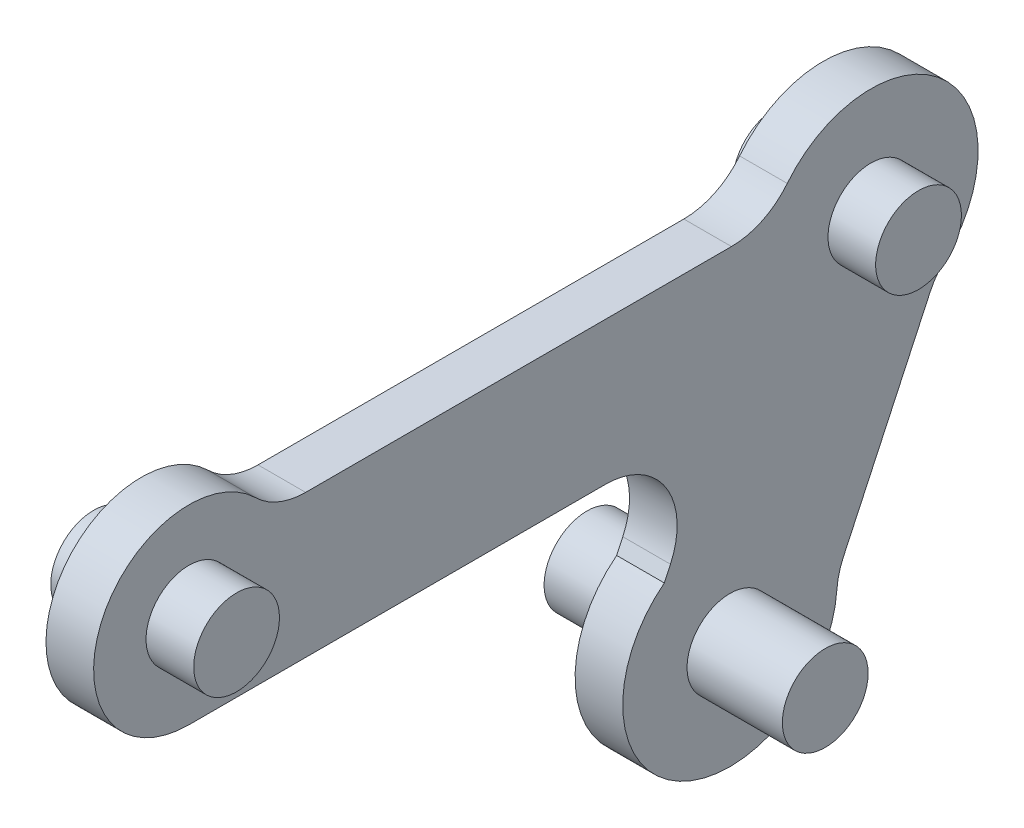
SolidWorks part; units mm, degrees
ref_plane "前视基准面" through (0, 0, 0) normal (0, 0, 1) x (1, 0, 0)
ref_plane "上视基准面" through (0, 0, 0) normal (0, 1, 0) x (1, 0, 0)
ref_plane "右视基准面" through (0, 0, 0) normal (1, 0, 0) x (0, 0, -1)
other "Configuration Table"
sketch "草图1" plane through (0, 0, 0) normal (1, 0, 0) x (0, 0, -1)
  line L1 (-25, 0) -> (0, 0)
  line L2 (-25, 0) -> (-25, -6)
  line L3 (-25, -6) -> (0, -6)
  line L4 (0, 0) -> (0, -6)
  line L5 (0, 0) -> (7.2505, -3.3809)
  line L6 (0, 0) -> (-5.9167, -12.6883)
  line L7 (-5.9167, -12.6883) -> (1.3338, -16.0693)
  line L8 (7.2505, -3.3809) -> (1.3338, -16.0693)
  circle A0 centre (-25, -2) radius 4
  circle A1 centre (3.6252, -1.6905) radius 4.5
  circle A2 centre (-2.2914, -14.3788) radius 4.5
  circle A3 centre (-25, -2) radius 2
  circle A4 centre (3.6252, -1.6905) radius 2
  circle A5 centre (-2.2914, -14.3788) radius 2
  dimension "D5" = 8
  dimension "D6" = 9
  dimension "D7" = 9
  dimension "D9" = 4
  dimension "D1" = 6
  dimension "D2" = 8
  dimension "D3" = 65
  dimension "D4" = 25
  dimension "D8" = 14
extrude "凸台-拉伸1" add sketch "草图1" along normal blind 2 contours A0 | L1 L4 L3 L2 | A1 | L5 L8 L7 L6 | A2
extrude "切除-拉伸1" cut sketch "草图1<3>" along normal through all contours A3 | A4 | A5
sketch "草图1<3>" plane through (0, 0, 0) normal (1, 0, 0) x (0, 0, -1) same geometry as "草图1"
fillet "圆角1" radius 3 5 edges at (1, -14.2009, -2.2051) (1, -5.2493, -6.3792) (1, 0, 0.5452) (1, 0, 21.5359) (1, -6, 2.7978)
sketch "草图2" plane through (2, 0, 0) normal (1, 0, 0) x (0, 0, -1)
  circle A0 centre (3.6252, -1.6905) radius 2
  circle A1 centre (-2.2914, -14.3788) radius 2
  circle A2 centre (-25, -2) radius 2
  circle A3 centre (3.6252, -1.6905) radius 1.8
  circle A4 centre (-2.2914, -14.3788) radius 1.8
  circle A5 centre (-25, -2) radius 1.8
  point P12 (0, 0)
  dimension "D1" = 4
  dimension "D2" = 3.6
extrude "凸台-拉伸2" add sketch "草图2" against normal up to surface (2 mm away) contours A2 | A0 | A1 up to face at (0, -2, 23)
extrude "凸台-拉伸5" add sketch "草图2<5>" along normal blind 2 contours A5 | A3 region at (2, -1.6905, -3.6252) region at (2, -2, 25)
sketch "草图2<5>" plane through (2, 0, 0) normal (1, 0, 0) x (0, 0, -1) same geometry as "草图2"
extrude "凸台-拉伸6" add sketch "草图2<6>" against normal blind 2 from surface contours A5 | A3 region at (2, -1.6905, -3.6252) region at (2, -2, 25) starting at face at (0, -5.8195, 6.0803)
sketch "草图2<6>" plane through (2, 0, 0) normal (1, 0, 0) x (0, 0, -1) same geometry as "草图2"
extrude "凸台-拉伸7" add sketch "草图2<7>" along normal blind 4 contours A4 region at (2, -14.3788, 2.2914)
sketch "草图2<7>" plane through (2, 0, 0) normal (1, 0, 0) x (0, 0, -1) same geometry as "草图2"
extrude "凸台-拉伸8" add sketch "草图2<8>" against normal blind 4 from surface contours A4 region at (2, -14.3788, 2.2914) starting at face at (0, -1.6905, -5.4252)
sketch "草图2<8>" plane through (2, 0, 0) normal (1, 0, 0) x (0, 0, -1) same geometry as "草图2"
